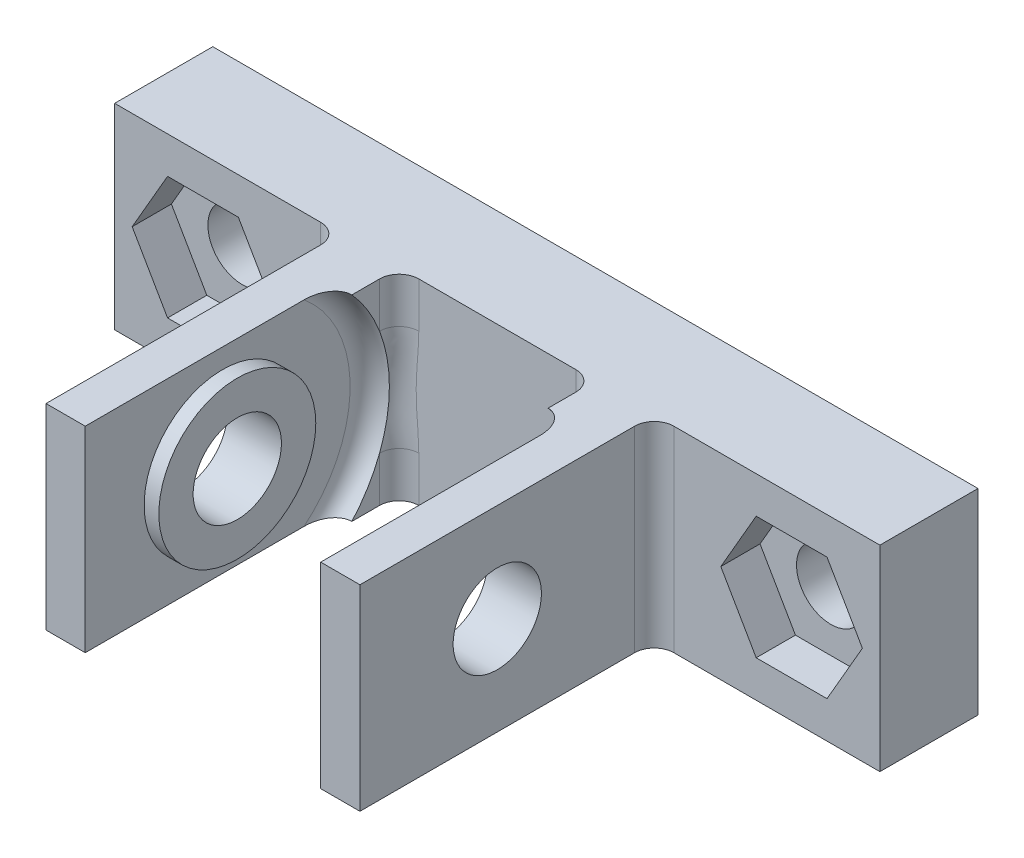
SolidWorks part; units mm, degrees
ref_plane "Front Plane" through (0, 0, 0) normal (0, 0, 1) x (1, 0, 0)
ref_plane "Top Plane" through (0, 0, 0) normal (0, 1, 0) x (1, 0, 0)
ref_plane "Right Plane" through (0, 0, 0) normal (1, 0, 0) x (0, 0, -1)
sketch "Sketch1" plane through (0, 0, 0) normal (0, 1, 0) x (1, 0, 0)
  line L0 (0, 0) -> (0, -20.0709) construction
  line L1 (-8, 0) -> (8, 0)
  line L2 (8, 0) -> (8, -20)
  line L3 (8, -20) -> (5, -20)
  line L4 (5, -20) -> (5, -5)
  line L5 (5, -5) -> (-5, -5)
  line L6 (-5, -20) -> (-5, -5)
  line L7 (-8, -20) -> (-5, -20)
  line L8 (-8, 0) -> (-8, -20)
  line L9 (5, -20) -> (5, -5)
  point P9 (0, -5)
  dimension "D1" = 5
  dimension "D2" = 3
  dimension "D3" = 15
  dimension "D4" = 5
extrude "Boss-Extrude1" add sketch "Sketch1" along normal blind 10 contours L1 L0 L5 L4 L3 L2 | L0 L1 L8 L7 L6 L5 region at (5.3235, 0, 7.7941) region at (-5.3235, 0, 7.7941)
sketch "Sketch2" plane through (8, 0, 0) normal (1, 0, 0) x (0, 0, -1)
  line L0 (-20, 5) -> (0, 5) construction
  line L1 (-20, 10) -> (-20, 0) construction
  line L2 (0, 10) -> (0, 0) construction
  circle A0 centre (-13, 5) radius 2.25
  dimension "D1" = 4.5
  dimension "D2" = 13
extrude "Cut-Extrude1" cut sketch "Sketch2" against normal through all contours A0
sketch "Sketch3" plane through (0, 10, 0) normal (0, 1, 0) x (1, 0, 0)
  line L1 (-19.5, -5) -> (19.5, -5)
  line L2 (0, 0) -> (0, -5) construction
  line L3 (-19.5, 0) -> (19.5, 0)
  line L4 (19.5, -5) -> (19.5, 0)
  line L5 (-8, 0) -> (8, 0) construction
  line L7 (-19.5, -5) -> (-19.5, 0)
  line L8 (5, -5) -> (-5, -5) construction
  dimension "D1" = 19.5
extrude "Boss-Extrude2" add sketch "Sketch3" against normal through all
sketch "Sketch4" plane through (0, 0, 5) normal (0, 0, 1) x (1, 0, 0)
  line L0 (-19.5, 5) -> (-8, 5) construction
  line L1 (-19.5, 0) -> (-19.5, 10) construction
  line L2 (-8, 10) -> (-8, 0) construction
  line L3 (-15, 0) -> (-15, 10) construction
  line L6 (0, 0) -> (0, 10) construction
  line L7 (5, 0) -> (-5, 0) construction
  line L8 (5, 10) -> (-5, 10) construction
  line L9 (15, 0) -> (15, 10) construction
  line L10 (19.5, 5) -> (8, 5) construction
  line L11 (-15, 0) -> (-15, 10) construction
  circle A0 centre (-15, 5) radius 1.75
  circle A1 centre (15, 5) radius 1.75
  dimension "D1" = 3.5
  dimension "D2" = 15
extrude "Cut-Extrude2" cut sketch "Sketch4" against normal through all
sketch "Sketch6" plane through (-5, 0, 0) normal (1, 0, 0) x (0, 0, -1)
  line L0 (-13, 12.5) -> (-20.5, 12.5)
  line L1 (-20.5, 12.5) -> (-20.5, 5)
  line L2 (-20.5, 5) -> (-20.5, -2.5)
  line L3 (-20.5, -2.5) -> (-13, -2.5)
  arc A0 (-13, -2.5) -> (-13, 12.5) centre (-13, 5) ccw
  circle A1 centre (-13, 5) radius 2.25 construction
  dimension "D1" = 15
extrude "Cut-Extrude3" cut sketch "Sketch6" against normal blind 1
sketch "Sketch5" plane through (-6, 0, 0) normal (1, 0, 0) x (0, 0, -1)
  circle A0 centre (-13, 5) radius 4
  circle A1 centre (-13, 5) radius 2.25
  circle A2 centre (-13, 5) radius 2.25 construction
  dimension "D1" = 8
extrude "Boss-Extrude3" add sketch "Sketch5" along normal blind 0.75
mirror "Mirror1" about plane through (0, 0, 0) normal (1, 0, 0) of "Boss-Extrude3", "Cut-Extrude3"
fillet "Fillet1" radius 1 6 edges at (-6, 5, 5.5) (6, 5, 5.5) (5, 5, 5) (-5, 5, 5) (8, 5, 5) (-8, 5, 5)
sketch "Sketch7" plane through (0, 0, 5) normal (0, 0, 1) x (1, 0, 0)
  line L0 (0, 10) -> (0, 0) construction
  line L1 (16.8042, 8.125) -> (13.1958, 8.125)
  line L2 (13.1958, 8.125) -> (11.3916, 5)
  line L3 (11.3916, 5) -> (13.1958, 1.875)
  line L4 (13.1958, 1.875) -> (16.8042, 1.875)
  line L5 (16.8042, 1.875) -> (18.6084, 5)
  line L6 (18.6084, 5) -> (16.8042, 8.125)
  line L7 (4, 10) -> (-4, 10) construction
  line L8 (-18.6084, 5) -> (-16.8042, 8.125)
  line L9 (-16.8042, 1.875) -> (-18.6084, 5)
  line L10 (-13.1958, 1.875) -> (-16.8042, 1.875)
  line L11 (-11.3916, 5) -> (-13.1958, 1.875)
  line L12 (-13.1958, 8.125) -> (-11.3916, 5)
  line L13 (-16.8042, 8.125) -> (-13.1958, 8.125)
  line L14 (18.6084, 5) -> (16.8042, 8.125)
  circle A0 centre (15, 5) radius 3.125 construction
  circle A1 centre (-15, 5) radius 3.125 construction
  circle M5 centre (15, 5) radius 1.75
  dimension "D1" = 6.25
extrude "Cut-Extrude4" cut sketch "Sketch7" against normal blind 2 contours L13 L8 L9 L10 L11 L12 | L5 L6 L1 L2 L3 L4 M5 | M5 region at (17.6236, 6.5148, 5) region at (-15, 5, 5) region at (15, 5, 5)
equation "\"X-ROD-SPACING\"=45"
equation "\"Y-ROD-SPACING\"=75"
equation "\"Z-ROD-SPACING\"=17.5"
equation "\"Y-BED-OFFSET\"=2"
equation "\"Y-BED-ROD-INSET\"=3.5"
equation "\"Y-BED-SCREW-SPACING\"=209"
equation "\"Y-BED-SCREW-CUTOUT-SLOT-HEIGHT\"=2"
equation "\"T-SLOT-NUT-FILLET-RADIUS\"=0.5"
equation "\"T-SLOT-SCREW-SHAFT-RADIUS\"=1.55"
equation "\"T-SLOT-SCREW-SHAFT-CUTOUT-LENGTH\"=11.0"
equation "\"T-SLOT-NUT-DEPTH\"=3.5"
equation "\"T-SLOT-NUT-WIDTH\"=2.85"
equation "\"T-SLOT-NUT-END-DISTANCE\"=8"
equation "\"ACRYLIC-THICKNESS\"=10"
equation "\"ACRYLIC-THICKNESS2\"=4.5"
equation "\"ACRYLIC-TAB-CUTOUT-SIZE\"=\"ACRYLIC-THICKNESS\"+\"ACRYLIC-TAB-TOLERANCE\"*2"
equation "\"ACRYLIC-TAB-TOLERANCE\"=-.05"
equation "\"KERF\"=0.1"
equation "\"ACRYLIC-THICKNESS-TAB-CUTOUT-WIDTH\"=\"ACRYLIC-THICKNESS\"-\"KERF\"*2"
equation "\"ACRYLIC-THICKNESS-TAB-CUTOUT-HEIGHT\"=\"ACRYLIC-TAB-WIDTH\"-\"KERF\"*4"
equation "\"ACRYLIC-THICKNESS2-TAB-CUTOUT-WIDTH\"=\"ACRYLIC-THICKNESS2\"-\"KERF\"*2"
equation "\"ACRYLIC-THICKNESS2-TAB-CUTOUT-HEIGHT\"=\"ACRYLIC-TAB-WIDTH\"-\"KERF\"*4"
equation "\"ACRYLIC-TAB-WIDTH\"=\"ACRYLIC-THICKNESS\""
equation "\"ACRYLIC-M3-HOLE\"=2.9"
equation "\"SMOOTHROD-CAP-SCREW-DISTANCE\"=20"
equation "\"FRAME-WIDTH-INNER\"=370"
equation "\"NEMA17-HOLE-SPACING\"=31"
equation "\"NEMA17-CENTRAL-CUTOUT\"=22.5"
equation "\"Z-BRACKET-REACH\"=55"
equation "\"Z-ROD-INSET\"=16"
equation "\"TOP-BRACKET-SPACING\"=40"
equation "\"SMOOTHROD-X-LENGTH\"=350"
equation "\"SMOOTHROD-Y-LENGTH\"=350"
equation "\"SMOOTHROD-Z-LENGTH\"=350"
equation "\"SMOOTHROD-TIGHTENING-HEADROOM\"=.25"
equation "\"LEADSCREW-Z-LENGTH\"=300"
equation "\"SCREW-LENGTH-FRAME\"=\"ACRYLIC-THICKNESS\" + 10"
equation "\"SCREW-LENGTH-MOTOR\"=\"ACRYLIC-THICKNESS\" + 5"
equation "\"SCREW-LENGTH-EXTRUDER\"=28"
equation "\"SCREW-HEAD-RADIUS\"=6"
equation "\"PRINTED-M3-HOLE\"=3.5"
equation "\"PRINTED-X-SMOOTHROD-DIAMETER\"=9.0"
equation "\"PRINTED-X-SMOOTHROD-CUTOUT\"=10"
equation "\"PRINTED-X-BASE-HEIGHT\"=10"
equation "\"PRINTED-LM8UU-CUTOUT-SIZE\"=15.5"
equation "\"PRINTED-LM8UU-CUTOUT-LENGTH\"=24.5"
equation "\"PRINTED-X-IDLER-HEIGHT\"=16"
equation "\"PRINTED-M3-NUT-AF\"=6.25"
equation "\"PSU-MOUNTING-WIDTH\"=95"
equation "\"PSU-MOUNTING-HEIGHT\"=177"
equation "\"Y-BELT-TO-ROD-DISTANCE\"=20"
equation "\"SPOOL-HOLDER-ROD-SPACING\"=150"
equation "\"ACRYLIC-X-CARRIAGE-WIDTH\"=55"
equation "\"ACRYLIC-X-CARRIAGE-HEIGHT\"=75"
equation "\"ACRYLIC-X-CARRIAGE-LM8UU-CUTOUT-WIDTH\"=24.25"
equation "\"ACRYLIC-X-CARRIAGE-LM8UU-CUTOUT-HEIGHT\"=11.0"
equation "\"ACRYLIC-X-CARRIAGE-SCREW-SPACING-X\"=15"
equation "\"ACRYLIC-X-CARRIAGE-SCREW-SPACING-Y\"=33"
equation "\"ACRYLIC-X-CARRIAGE-CENTER-TAB-SPACING\"=14"
equation "\"ACRYLIC-X-CARRIAGE-EXTRUDER-OFFSET\"=26"
equation "\"ACRYLIC-X-CARRIAGE-EXTRUDER-ANGLE\"=90"
equation "\"ACRYLIC-X-CARRIAGE-EXTRUDER-SHELF-DEPTH\"=\"ACRYLIC-X-CARRIAGE-EXTRUDER-OFFSET\" + 28"
equation "\"ACRYLIC-X-CARRIAGE-EXTRUDER-BRACE-SPACING\"=23"
equation "\"ACRYLIC-X-CARRIAGE-EXTRUDER-BRACE-TAB-OFFSET\"=20"
equation "\"ACRYLIC-X-CARRIAGE-EXTRUDER-BRACE-HEIGHT\"=35"
equation "\"ACRYLIC-X-CARRIAGE-EXTRUDER-BRACE-SCREW-SPACING\"=22"
equation "\"ACRYLIC-X-CARRIAGE-DUAL-WIDTH-MULTIPLIER\"=1.65"
equation "\"ACRYLIC-X-CARRIAGE-DUAL-HOTEND-SPACING\"=42"
equation "\"ACRYLIC-X-CARRIAGE-DUAL-WIDTH\"=75"
equation "\"ACRYLIC-X-CARRIAGE-DUAL-FAN-OFFSET\"=52"
equation "\"ACRYLIC-X-CARRIAGE-DUAL-FAN-HEIGHT\"=20"
equation "\"ACRYLIC-X-CARRIAGE-DUAL-HOTEND-SEPARATION\"=36"
equation "\"ACRYLIC-X-CARRIAGE-DUAL-MOUNT-PLATE-DEPTH\"=75"
equation "\"ACRYLIC-X-CARRIAGE-DUAL-MOUNT-BRACE-WIDTH\"=33"
equation "\"ACRYLIC-X-CARRIAGE-DUAL-MOUNT-SCREW-WIDTH\"=40"
equation "\"BLOWER-FAN-WIDTH\"=15"
equation "\"D1@Sketch7\"=\"PRINTED-M3-NUT-AF\""
